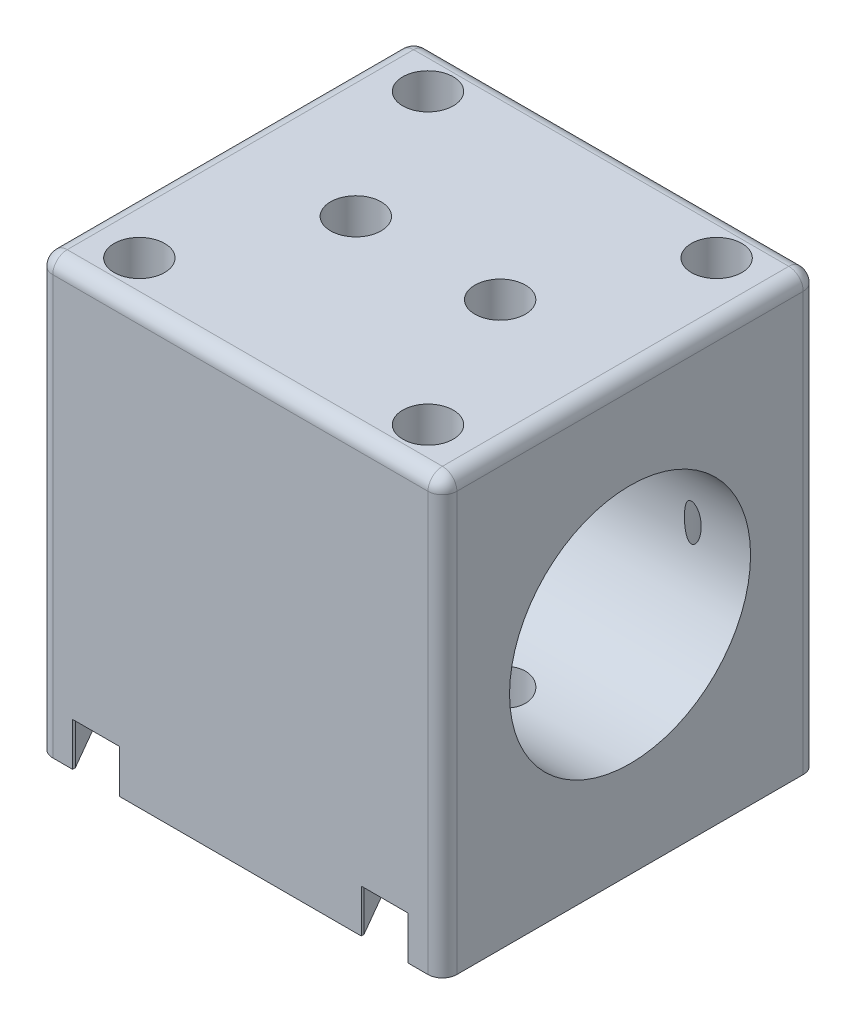
SolidWorks part; units mm, degrees
ref_plane "Front Plane" through (0, 0, 0) normal (0, 0, 1) x (1, 0, 0)
ref_plane "Top Plane" through (0, 0, 0) normal (0, 1, 0) x (1, 0, 0)
ref_plane "Right Plane" through (0, 0, 0) normal (1, 0, 0) x (0, 0, -1)
sketch "Sketch1" plane through (0, 0, 0) normal (1, 0, 0) x (0, 0, -1)
  line L0 (0, 8) -> (0, 15) construction
  line L1 (-13, -15) -> (13, -15)
  line L2 (-13, -15) -> (-13, 15)
  line L3 (-13, 15) -> (13, 15)
  line L4 (13, -15) -> (13, 15)
  line L5 (-13, -15) -> (13, 15) construction
  line L6 (-13, 15) -> (13, -15) construction
  circle A0 centre (0, 0) radius 8
  dimension "D1" = 16
  dimension "D2" = 30
  dimension "D3" = 26
extrude "Boss-Extrude1" add sketch "Sketch1" along normal mid plane 28
sketch "Sketch2" plane through (0, 15, 0) normal (0, 1, 0) x (1, 0, 0)
  line L1 (10, -10) -> (-10, -10) construction
  line L2 (10, -10) -> (10, 10) construction
  line L3 (10, 10) -> (-10, 10) construction
  line L4 (-10, -10) -> (-10, 10) construction
  line L5 (10, -10) -> (-10, 10) construction
  line L6 (10, 10) -> (-10, -10) construction
  circle A0 centre (-10, 10) radius 1.75
  circle A1 centre (10, 10) radius 1.75
  circle A2 centre (10, -10) radius 1.75
  circle A3 centre (-10, -10) radius 1.75
  point P0 (0, 0)
  dimension "D3" = 3.5
  dimension "D1" = 20
  dimension "D2" = 20
extrude "Cut-Extrude1" cut sketch "Sketch2" against normal blind 32
sketch "Sketch5" plane through (-14, 0, 0) normal (-1, 0, 0) x (0, 0, 1)
  circle A2 centre (0, 0) radius 6
  circle A4 centre (0, 0) radius 8.5
  dimension "D1" = 17
extrude "Boss-Extrude3" add sketch "Sketch5" against normal blind 3
fillet "Fillet3" radius 1 8 edges at (-14, 0, 13) (14, 0, 13) (-14, 0, -13) (-14, 15, 0) (0, 15, 13) (14, 0, -13) (0, 15, -13) (14, 15, 0)
sketch "Sketch6" plane through (0, -15, 0) normal (0, -1, 0) x (1, 0, 0)
  line L0 (-11.625, 12.8146) -> (-11.625, 13.1816)
  line L1 (-6.75, 10) -> (-8.375, 12.8146)
  line L3 (-11.625, 12.8146) -> (-13.25, 10)
  line L4 (-13.25, 10) -> (-11.625, 7.1854)
  line L5 (-11.625, 7.1854) -> (-8.375, 7.1854)
  line L6 (-8.375, 7.1854) -> (-6.75, 10)
  line L7 (-11.625, 13.1816) -> (-8.375, 13.1816)
  line L8 (-8.375, 13.1816) -> (-8.375, 12.8146)
  line L9 (-10, 10) -> (10, 10) construction
  line L10 (-8.375, 12.8146) -> (-10, 12.8146) [skipped]
  line L11 (-10, 10) -> (-10, -10) construction
  line L12 (-10, -10) -> (10, -10) construction
  line L13 (10, -10) -> (10, 10) construction
  line L14 (8.375, 13.1816) -> (8.375, 12.8146)
  line L15 (10, 0) -> (-10, 0) construction
  line L16 (11.625, 13.1816) -> (8.375, 13.1816)
  line L17 (0, 10) -> (0, -10) construction
  line L18 (8.375, 7.1854) -> (6.75, 10)
  line L19 (11.625, 7.1854) -> (8.375, 7.1854)
  line L20 (13.25, 10) -> (11.625, 7.1854)
  line L21 (11.625, 12.8146) -> (13.25, 10)
  line L22 (6.75, 10) -> (8.375, 12.8146)
  line L23 (11.625, 12.8146) -> (11.625, 13.1816)
  line L24 (11.625, -12.8146) -> (11.625, -13.1816)
  line L25 (6.75, -10) -> (8.375, -12.8146)
  line L26 (11.625, -12.8146) -> (13.25, -10)
  line L27 (13.25, -10) -> (11.625, -7.1854)
  line L28 (11.625, -7.1854) -> (8.375, -7.1854)
  line L29 (8.375, -7.1854) -> (6.75, -10)
  line L30 (11.625, -13.1816) -> (8.375, -13.1816)
  line L31 (8.375, -13.1816) -> (8.375, -12.8146)
  line L32 (-8.375, -13.1816) -> (-8.375, -12.8146)
  line L33 (-11.625, -13.1816) -> (-8.375, -13.1816)
  line L34 (-8.375, -7.1854) -> (-6.75, -10)
  line L35 (-11.625, -7.1854) -> (-8.375, -7.1854)
  line L36 (-13.25, -10) -> (-11.625, -7.1854)
  line L37 (-11.625, -12.8146) -> (-13.25, -10)
  line L38 (-6.75, -10) -> (-8.375, -12.8146)
  line L39 (-11.625, -12.8146) -> (-11.625, -13.1816)
  circle A0 centre (-10, 10) radius 2.8146 construction
  circle A1 centre (10, 10) radius 2.8146 construction
  circle A2 centre (10, -10) radius 2.8146 construction
  circle A3 centre (-10, -10) radius 2.8146 construction
  dimension "D1" = 6.5
extrude "Cut-Extrude2" cut sketch "Sketch6" against normal blind 3
sketch "Sketch7" plane through (0, 15, 0) normal (0, 1, 0) x (1, 0, 0)
  line L0 (10, 10) -> (10, -10) construction
  line L1 (10, -10) -> (-10, -10) construction
  line L2 (-10, -10) -> (-10, 10) construction
  line L3 (-10, 10) -> (10, 10) construction
  line L4 (0, 0) -> (-10, 0) construction
  line L8 (10, 0) -> (0, 0) construction
  circle A0 centre (5, 0) radius 1.75
  circle A1 centre (-5, 0) radius 1.75
  dimension "D1" = 3.5
extrude "Cut-Extrude3" cut sketch "Sketch7" against normal up to surface (30 mm away) up to face at (0, -15, 0)
sketch "Sketch8" plane through (0, -15, 0) normal (0, -1, 0) x (1, 0, 0)
  line L0 (-5, 0) -> (5, 0) construction
  line L1 (-1.75, 0) -> (-3.375, 2.8146)
  line L2 (-3.375, 2.8146) -> (-6.625, 2.8146)
  line L3 (-6.625, 2.8146) -> (-8.25, 0)
  line L4 (-8.25, 0) -> (-6.625, -2.8146)
  line L5 (-6.625, -2.8146) -> (-3.375, -2.8146)
  line L6 (-3.375, -2.8146) -> (-1.75, 0)
  line L7 (0, 0) -> (0, 5.5898) construction
  line L8 (3.375, -2.8146) -> (1.75, 0)
  line L9 (6.625, -2.8146) -> (3.375, -2.8146)
  line L10 (8.25, 0) -> (6.625, -2.8146)
  line L11 (6.625, 2.8146) -> (8.25, 0)
  line L12 (3.375, 2.8146) -> (6.625, 2.8146)
  line L13 (1.75, 0) -> (3.375, 2.8146)
  line L14 (-5, 4.5) -> (5, 4.5)
  line L15 (5, -4.5) -> (-5, -4.5)
  circle A0 centre (-5, 0) radius 2.8146 construction
  circle A1 centre (5, 0) radius 2.8146 construction
  arc A2 (-5, 4.5) -> (-5, -4.5) centre (-5, 0) ccw
  arc A3 (5, -4.5) -> (5, 4.5) centre (5, 0) ccw
  dimension "D2" = 9
  dimension "D3" = 9
  dimension "D1" = 6.5
extrude "Boss-Extrude4" add sketch "Sketch8" along normal blind 3
fillet "Fillet4" radius 1 4 edges at (9.5, -15, 0) (0, -15, -4.5) (-9.5, -15, 0) (0, -15, 4.5)
sketch "Sketch9" plane through (14, 0, 0) normal (1, 0, 0) x (0, 0, -1)
  circle A0 centre (0, 0) radius 8.35
  dimension "D1" = 16.7
extrude "Cut-Extrude4" cut sketch "Sketch9" against normal up to surface (25 mm away) up to face at (-11, 0, 6)
